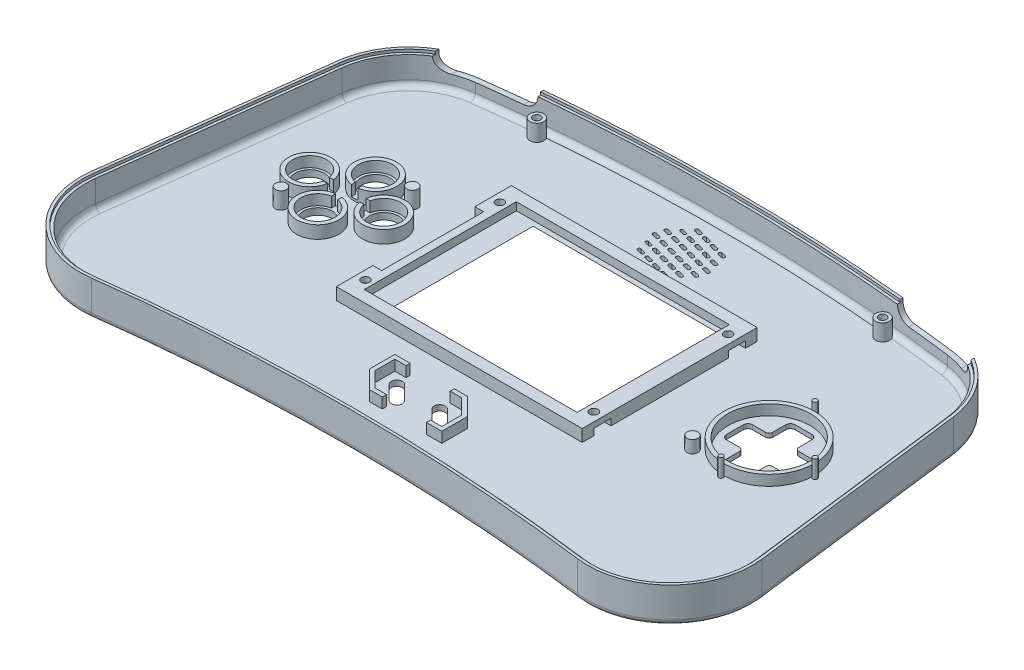
SolidWorks part; units mm, degrees
ref_plane "Plan de face" through (0, 0, 0) normal (0, 0, 1) x (1, 0, 0)
ref_plane "Plan de dessus" through (0, 0, 0) normal (0, 1, 0) x (1, 0, 0)
ref_plane "Plan de droite" through (0, 0, 0) normal (1, 0, 0) x (0, 0, -1)
sketch "Esquisse fond coque" plane through (0, 0, 0) normal (0, 1, 0) x (1, 0, 0)
  line L0 (-122.2671, -38.9175) -> (-112.2671, 40.8662)
  line L1 (112.2671, 40.8662) -> (122.2671, -38.9175)
  line L2 (-103.7302, 58.3314) -> (113.6596, -63.9151) construction
  line L3 (-113.6596, -63.9151) -> (103.7302, 58.3314) construction
  arc A0 (-112.2671, 40.8662) -> (-86.2786, 66.8963) centre (-82.5, 37.1352) cw
  arc A1 (-86.2786, 66.8963) -> (86.2786, 66.8963) centre (0, -612.6484) cw
  arc A2 (86.2786, 66.8963) -> (112.2671, 40.8662) centre (82.5, 37.1352) cw
  arc A3 (-122.2671, -38.9175) -> (-88.6189, -72.3963) centre (-92.5, -42.6484) ccw
  arc A4 (122.2671, -38.9175) -> (88.6189, -72.3963) centre (92.5, -42.6484) cw
  arc A5 (88.6189, -72.3963) -> (-88.6189, -72.3963) centre (0, -751.6398) ccw
  point P14 (122.5, -42.6484)
  point P15 (92.5, -72.6484)
  point P16 (-122.5, -42.6484)
  point P17 (0, 72.3516)
  point P18 (0, -66.6398)
  point P23 (0, 0)
  dimension "D4" = 30
  dimension "D5" = 30
  dimension "D6" = 685
  dimension "D7" = 685
  dimension "D1" = 245
  dimension "D2" = 165
  dimension "D3" = 145
extrude "Fond coque" add sketch "Esquisse fond coque" along normal blind 2
sketch "Esquisse contour coque" plane through (0, 2, 0) normal (0, 1, 0) x (1, 0, 0)
  line L0 (-120.2826, -39.1662) -> (-110.2826, 40.6174)
  line L1 (110.2826, 40.6174) -> (120.2826, -39.1662)
  line L2 (122.2671, -38.9175) -> (112.2671, 40.8662) construction
  line L3 (-112.2671, 40.8662) -> (-122.2671, -38.9175) construction
  line L4 (-122.2671, -38.9175) -> (-112.2671, 40.8662)
  line L5 (112.2671, 40.8662) -> (122.2671, -38.9175)
  arc A0 (-110.2826, 40.6174) -> (-86.0267, 64.9122) centre (-82.5, 37.1352) cw
  arc A1 (-86.0267, 64.9122) -> (86.0267, 64.9122) centre (0, -612.6484) cw
  arc A2 (86.0267, 64.9122) -> (110.2826, 40.6174) centre (82.5, 37.1352) cw
  arc A3 (120.2826, -39.1662) -> (88.8776, -70.4131) centre (92.5, -42.6484) cw
  arc A4 (-120.2826, -39.1662) -> (-88.8776, -70.4131) centre (-92.5, -42.6484) ccw
  arc A5 (-88.8776, -70.4131) -> (88.8776, -70.4131) centre (0, -751.6398) cw
  arc A6 (86.2786, 66.8963) -> (-86.2786, 66.8963) centre (0, -612.6484) ccw construction
  arc A7 (88.6189, -72.3963) -> (-88.6189, -72.3963) centre (0, -751.6398) ccw construction
  arc A8 (-88.6189, -72.3963) -> (-122.2671, -38.9175) centre (-92.5, -42.6484) cw
  arc A9 (-122.2671, -38.9175) -> (-88.6189, -72.3963) centre (-92.5, -42.6484) ccw construction
  arc A10 (88.6189, -72.3963) -> (122.2671, -38.9175) centre (92.5, -42.6484) ccw
  arc A11 (88.6189, -72.3963) -> (122.2671, -38.9175) centre (92.5, -42.6484) ccw construction
  arc A12 (-112.2671, 40.8662) -> (-86.2786, 66.8963) centre (-82.5, 37.1352) cw
  arc A13 (-86.2786, 66.8963) -> (-112.2671, 40.8662) centre (-82.5, 37.1352) ccw construction
  arc A14 (86.2786, 66.8963) -> (112.2671, 40.8662) centre (82.5, 37.1352) cw
  arc A15 (112.2671, 40.8662) -> (86.2786, 66.8963) centre (82.5, 37.1352) ccw construction
  arc A16 (-88.6189, -72.3963) -> (88.6189, -72.3963) centre (0, -751.6398) cw
  arc A17 (-86.2786, 66.8963) -> (86.2786, 66.8963) centre (0, -612.6484) cw
  point P6 (0, 70.3516)
  point P14 (0, -64.6398)
  point P18 (0, 72.3516)
  point P23 (0, -66.6398)
  point P31 (-113.6596, -63.9151)
  point P36 (-113.6596, -63.9151)
  point P37 (0, -66.6398)
  point P39 (113.6596, -63.9151)
  point P45 (113.6596, -63.9151)
  point P54 (-103.7302, 58.3314)
  point P55 (-103.7302, 58.3314)
  point P58 (103.7302, 58.3314)
  point P64 (103.7302, 58.3314)
  point P66 (0, 72.3516)
  dimension "D1" = 2
  dimension "D2" = 2
  dimension "D3" = 2
  dimension "D4" = 2
extrude "Contour coque" add sketch "Esquisse contour coque" along normal blind 10
fillet "Congé1" radius 2 8 edges at (-115.2826, 2, -0.7256) (-102.3148, 2, -56.9183) (0, 2, -70.3516) (102.3148, 2, -56.9183) (115.2826, 2, -0.7256) (112.249, 2, 62.4973) (0, 2, 64.6398) (-112.249, 2, 62.4973)
fillet "Congé2" radius 2 8 edges at (0, 0, 66.6398) (113.6596, 0, 63.9151) (117.2671, 0, -0.9743) (103.7302, 0, -58.3314) (0, 0, -72.3516) (-103.7302, 0, -58.3314) (-117.2671, 0, -0.9743) (-113.6596, 0, 63.9151)
sketch "Esquisse cavité écrou" plane through (0, 0, 0) normal (0, -1, 0) x (1, 0, 0)
  line L1 (33.91, 17.87) -> (-33.91, 17.87)
  line L2 (33.91, 17.87) -> (33.91, -33.87)
  line L3 (33.91, -33.87) -> (-33.91, -33.87)
  line L4 (-33.91, 17.87) -> (-33.91, -33.87)
  line L5 (33.91, 17.87) -> (-33.91, -33.87) construction
  line L6 (33.91, -33.87) -> (-33.91, 17.87) construction
  point P0 (0, -8)
  dimension "D1" = 67.82
  dimension "D2" = 51.74
  dimension "D3" = 8
extrude "Cavité écran" cut sketch "Esquisse cavité écrou" against normal blind 3.55
sketch "Esquisse glissières écran" plane through (0, 2, 0) normal (0, 1, 0) x (1, 0, 0)
  line L1 (-47.84, -23.87) -> (41.72, -23.87)
  line L2 (-47.84, -23.87) -> (-47.84, -19.58)
  line L4 (41.72, -23.87) -> (41.72, -19.58)
  line L29 (-33.91, -17.87) -> (33.91, -17.87) construction
  line L30 (41.72, 35.58) -> (41.72, 39.87)
  line L31 (-33.91, 33.87) -> (-33.91, -17.87) construction
  line L32 (33.91, -17.87) -> (33.91, 33.87) construction
  line L35 (33.91, 33.87) -> (-33.91, 33.87) construction
  line L36 (-47.84, 39.87) -> (41.72, 39.87)
  line L37 (-47.84, 35.58) -> (-44.64, 35.58)
  line L38 (-44.64, 35.58) -> (-41.9553, 34.03)
  line L39 (-47.84, -13.38) -> (-44.64, -13.38)
  line L40 (-44.64, -13.38) -> (-41.9553, -14.93)
  line L41 (35.8353, -14.93) -> (35.8353, -18.03)
  line L42 (35.8353, -18.03) -> (38.52, -19.58)
  line L44 (35.8353, 34.03) -> (35.8353, 30.93)
  line L45 (35.8353, 30.93) -> (38.52, 29.38)
  line L46 (33.91, 33.87) -> (-33.91, 33.87) construction
  line L49 (38.52, 29.38) -> (41.72, 29.38)
  line L50 (35.8353, 34.03) -> (38.52, 35.58)
  line L53 (38.52, -19.58) -> (41.72, -19.58)
  line L60 (-41.9553, -14.93) -> (-41.9553, -18.03)
  line L65 (-41.9553, 34.03) -> (-41.9553, 30.93)
  line L66 (-41.9553, 30.93) -> (-44.64, 29.38)
  line L69 (-41.9553, -18.03) -> (-44.64, -19.58)
  line L70 (-33.91, 33.87) -> (33.91, 33.87)
  line L71 (-33.91, 33.87) -> (-33.91, -17.87)
  line L72 (-33.91, -17.87) -> (33.91, -17.87)
  line L73 (33.91, 33.87) -> (33.91, -17.87)
  line L74 (-44.64, -19.58) -> (-47.84, -19.58)
  line L75 (-47.84, -13.38) -> (-47.84, -10.555)
  line L76 (-44.64, 29.38) -> (-47.84, 29.38)
  line L77 (-47.84, 35.58) -> (-47.84, 39.87)
  line L78 (38.52, 35.58) -> (41.72, 35.58)
  line L79 (38.52, 29.38) -> (38.52, 32.48) construction
  line L80 (38.52, 32.48) -> (38.52, 35.58) construction
  line L81 (35.8353, -14.93) -> (38.52, -13.38)
  line L82 (38.52, -13.38) -> (41.72, -13.38)
  line L83 (38.52, -19.58) -> (38.52, -16.48) construction
  line L84 (38.52, -16.48) -> (38.52, -13.38) construction
  line L85 (41.72, -13.38) -> (41.72, 29.38)
  line L86 (-47.84, 26.555) -> (-44.64, 26.555)
  line L87 (-44.64, 26.555) -> (-44.64, -10.555)
  line L88 (-44.64, -10.555) -> (-47.84, -10.555)
  line L90 (-47.84, 26.555) -> (-47.84, 29.38)
  point P4 (-44.64, 32.48)
  point P12 (38.52, -16.48)
  point P16 (-44.64, -16.48)
  point P18 (38.52, 32.48)
  point P40 (-41.9553, -16.48)
  point P41 (-44.64, 8)
  point P49 (-41.9553, 32.48)
  point P55 (-33.91, 8)
  point P56 (35.8353, 32.48)
  dimension "D2" = 4.61
  dimension "D3" = 6.2
  dimension "D4" = 6.2
  dimension "D5" = 6
  dimension "D6" = 10.73
  dimension "D7" = 3.1
  dimension "D8" = 4.61
  dimension "D9" = 1.39
  dimension "D10" = 10.73
  dimension "D11" = 6.2
  dimension "D12" = 1.39
  dimension "D13" = 6.2
  dimension "D14" = 1.39
  dimension "D15" = 3.2
  dimension "D16" = 3.1
  dimension "D17" = 1.39
  dimension "D18" = 3.2
  dimension "D19" = 3.1
  dimension "D20" = 6
  dimension "D21" = 3.1
  dimension "D22" = 37.11
extrude "Glissières écran" add sketch "Esquisse glissières écran" along normal blind 1.55
chamfer "Chanfrein écran" distance 3.55 angle 45 4 edges at (33.91, 0, -8) (0, 0, 17.87) (-33.91, 0, -8) (0, 0, -33.87)
sketch "Esquisse surélévation écran" plane through (0, 3.55, 0) normal (0, 1, 0) x (1, 0, 0)
  line L0 (-41.84, 35.7) -> (-41.84, -19.7)
  line L1 (-33.91, 33.87) -> (-33.91, -17.87) construction
  line L2 (-47.84, 39.87) -> (-47.84, 35.58)
  line L3 (41.72, 39.87) -> (-47.84, 39.87) construction
  line L4 (-47.84, 35.58) -> (-44.64, 35.58)
  line L5 (-44.64, 35.58) -> (-41.9553, 34.03)
  line L6 (-44.64, 35.58) -> (-41.9553, 34.03) construction
  line L7 (-41.9553, 34.03) -> (-41.9553, 30.93)
  line L8 (-41.9553, 30.93) -> (-44.64, 29.38)
  line L9 (-44.64, 29.38) -> (-47.84, 29.38)
  line L10 (-47.84, 29.38) -> (-47.84, 26.555)
  line L11 (-47.84, -10.555) -> (-47.84, -13.38) construction
  line L14 (-47.84, 26.555) -> (-44.64, 26.555)
  line L15 (-47.84, -13.38) -> (-44.64, -13.38)
  line L16 (-44.64, -13.38) -> (-41.9553, -14.93)
  line L17 (-41.9553, -14.93) -> (-41.9553, -18.03)
  line L18 (-41.9553, -18.03) -> (-44.64, -19.58)
  line L19 (-44.64, -19.58) -> (-47.84, -19.58)
  line L20 (-47.84, -19.58) -> (-47.84, -23.87)
  line L21 (35.72, 35.7) -> (35.72, -19.7)
  line L22 (-44.64, 26.555) -> (-44.64, -10.555)
  line L24 (41.72, 39.87) -> (41.72, 35.58)
  line L25 (41.72, 35.58) -> (38.52, 35.58)
  line L26 (38.52, 35.58) -> (35.8353, 34.03)
  line L27 (35.8353, 34.03) -> (35.8353, 30.93)
  line L28 (35.8353, 30.93) -> (38.52, 29.38)
  line L29 (38.52, 29.38) -> (41.72, 29.38)
  line L30 (41.72, 29.38) -> (41.72, -13.38)
  line L31 (41.72, -13.38) -> (38.52, -13.38)
  line L32 (38.52, -13.38) -> (35.8353, -14.93)
  line L33 (35.8353, -14.93) -> (35.8353, -18.03)
  line L34 (35.8353, -18.03) -> (38.52, -19.58)
  line L35 (38.52, -19.58) -> (41.72, -19.58)
  line L36 (41.72, -19.58) -> (41.72, -23.87)
  line L38 (-47.84, -23.87) -> (41.72, -23.87)
  line L40 (-41.84, -19.7) -> (35.72, -19.7)
  line L42 (-47.84, 39.87) -> (41.72, 39.87)
  line L44 (-41.84, 35.7) -> (35.72, 35.7)
  line L45 (-44.64, -10.555) -> (-47.84, -10.555)
  line L46 (-47.84, -10.555) -> (-47.84, -13.38)
  point P1 (-41.84, 8)
  point P29 (-33.91, 8)
  dimension "D1" = 2.8
  dimension "D2" = 2.8
  dimension "D3" = 55.4
extrude "Surélévation écran" add sketch "Esquisse surélévation écran" along normal blind 0.8
sketch "Esquisse support écran" plane through (0, 4.35, 0) normal (0, 1, 0) x (1, 0, 0)
  line L0 (-47.84, -10.555) -> (-47.84, -23.87)
  line L1 (-47.84, -19.58) -> (-47.84, -23.87) construction
  line L2 (-47.84, -23.87) -> (41.72, -23.87) construction
  line L3 (-47.84, -23.87) -> (41.72, -23.87)
  line L4 (41.72, -23.87) -> (41.72, 39.87)
  line L5 (41.72, 39.87) -> (-47.84, 39.87)
  line L6 (-47.84, 39.87) -> (-47.84, 35.58) construction
  line L7 (41.72, 39.87) -> (-47.84, 39.87) construction
  line L8 (-47.84, 39.87) -> (-47.84, 26.555)
  line L9 (-41.84, -19.7) -> (35.72, -19.7)
  line L10 (35.72, -19.7) -> (35.72, 35.7)
  line L11 (35.72, 35.7) -> (-41.84, 35.7)
  line L12 (-41.84, 35.7) -> (-41.84, -19.7)
  line L13 (35.8353, 30.93) -> (35.8353, 34.03) construction
  line L14 (35.8353, -18.03) -> (35.8353, -14.93) construction
  line L15 (-41.9553, -14.93) -> (-41.9553, -18.03) construction
  line L16 (-41.9553, 34.03) -> (-41.9553, 30.93) construction
  line L17 (-47.84, 26.555) -> (-44.64, 26.555)
  line L19 (-47.84, -10.555) -> (-44.64, -10.555)
  line L20 (-44.64, 26.555) -> (-44.64, -10.555)
  circle A0 centre (-44.64, 32.48) radius 1.5
  circle A1 centre (-44.64, -16.48) radius 1.5
  circle A2 centre (38.52, -16.48) radius 1.5
  circle A3 centre (38.52, 32.48) radius 1.5
  point P35 (35.8353, 32.48)
  point P39 (35.8353, -16.48)
  point P43 (-41.9553, -16.48)
  point P46 (-41.9553, 32.48)
  dimension "D1" = 3
  dimension "D2" = 3
  dimension "D3" = 3
  dimension "D4" = 3
extrude "Support écran" add sketch "Esquisse support écran" along normal blind 2.05
sketch "Esquisse cavités ABXY" plane through (0, 0, 0) normal (0, -1, 0) x (1, 0, 0)
  line L0 (-75.96, -18.5) -> (-75.96, 2.5) construction
  line L1 (-62.46, -8) -> (-89.46, -8) construction
  line L2 (-37.46, -37.42) -> (-37.46, 21.42) construction
  circle A0 centre (-75.96, -18.5) radius 5.3
  circle A1 centre (-75.96, 2.5) radius 5.3
  circle A2 centre (-62.46, -8) radius 5.3
  circle A3 centre (-89.46, -8) radius 5.3
  point P8 (-75.96, -8)
  point P12 (-37.46, -8)
  dimension "D1" = 10.6
  dimension "D2" = 10.6
  dimension "D3" = 10.6
  dimension "D4" = 10.6
  dimension "D5" = 21
  dimension "D6" = 27
  dimension "D8" = 38.5
extrude "Cavités ABXY" cut sketch "Esquisse cavités ABXY" against normal blind 2.05
sketch "Esquisse abaissement ABXY" plane through (0, 0, 0) normal (0, -1, 0) x (-1, 0, 0)
  line L0 (75.9195, 18.4685) -> (62.5005, 8.0315) construction
  line L1 (79.9101, 13.3377) -> (66.4911, 2.9007)
  line L2 (71.9289, 23.5993) -> (58.5099, 13.1623)
  line L3 (75.96, 18.5) -> (62.46, 8) construction
  line L4 (76.0005, -2.4685) -> (89.4195, 7.9685) construction
  line L5 (72.0099, 2.6623) -> (85.4289, 13.0993)
  line L6 (79.9911, -7.5993) -> (93.4101, 2.8377)
  line L7 (75.96, -2.5) -> (89.46, 8) construction
  arc A0 (79.9101, 13.3377) -> (71.9289, 23.5993) centre (75.9195, 18.4685) ccw
  arc A1 (58.5099, 13.1623) -> (66.4911, 2.9007) centre (62.5005, 8.0315) ccw
  arc A2 (72.0099, 2.6623) -> (79.9911, -7.5993) centre (76.0005, -2.4685) ccw
  arc A3 (93.4101, 2.8377) -> (85.4289, 13.0993) centre (89.4195, 7.9685) ccw
  circle A4 centre (62.46, 8) radius 5.3
  circle A5 centre (75.96, 18.5) radius 5.3
  circle A6 centre (75.96, 18.5) radius 5.3 construction
  circle A7 centre (62.46, 8) radius 5.3 construction
  circle A8 centre (75.96, -2.5) radius 5.3
  circle A9 centre (89.46, 8) radius 5.3
  circle A12 centre (75.96, -2.5) radius 5.3 construction
  circle A13 centre (89.46, 8) radius 5.3 construction
  point P2 (69.21, 13.25)
  point P7 (57.3697, 4.0409)
  point P8 (81.0503, 22.4591)
  point P11 (69.21, 13.25)
  point P16 (82.71, 2.75)
  point P25 (82.71, 2.75)
  point P26 (70.8697, -6.4591)
  point P27 (94.5503, 11.9591)
  dimension "D1" = 13
  dimension "D2" = 30
  dimension "D3" = 13
  dimension "D4" = 30
extrude "Enlèv. mat.-Extru.4" cut sketch "Esquisse abaissement ABXY" against normal blind 0.4
sketch "Esquisse support ABXY" plane through (0, 2, 0) normal (0, 1, 0) x (1, 0, 0)
  circle A0 centre (-75.96, 18.5) radius 6.2
  circle A1 centre (-75.96, 18.5) radius 7.7
  circle A2 centre (-89.46, 8) radius 6.2
  circle A3 centre (-89.46, 8) radius 7.7
  circle A4 centre (-75.96, -2.5) radius 6.2
  circle A5 centre (-62.46, 8) radius 6.2
  circle A6 centre (-75.96, -2.5) radius 7.7
  circle A7 centre (-62.46, 8) radius 7.7
  point P4 (-82.16, 18.5)
  point P5 (-83.66, 18.5)
  point P10 (-95.66, 8)
  point P11 (-97.16, 8)
  point P20 (-82.16, -2.5)
  point P21 (-83.66, -2.5)
  point P22 (-68.66, 8)
  point P23 (-70.16, 8)
  dimension "D1" = 12.4
  dimension "D3" = 12.4
  dimension "D5" = 12.4
  dimension "D6" = 12.4
  dimension "D2" = 1.5
  dimension "D4" = 1.5
  dimension "D7" = 1.5
  dimension "D8" = 1.5
extrude "Support ABXY" add sketch "Esquisse support ABXY" along normal blind 4.6
sketch "Esquisse bloquage ABXY" plane through (0, 2, 0) normal (0, 1, 0) x (1, 0, 0)
  line L0 (-75.96, 18.5) -> (-75.96, -2.5) construction
  line L1 (-74.81, 3) -> (-77.11, 3)
  line L2 (-74.81, 3) -> (-74.81, 6.85)
  line L3 (-74.81, 13) -> (-77.11, 13)
  line L4 (-77.11, 3) -> (-77.11, 6.85)
  line L5 (-77.11, 9.15) -> (-74.81, 6.85) construction
  line L6 (-74.81, 9.15) -> (-77.11, 6.85) construction
  line L7 (-62.46, 8) -> (-89.46, 8) construction
  line L8 (-77.11, 9.15) -> (-77.11, 13)
  line L9 (-83.96, 6.85) -> (-77.11, 6.85)
  line L10 (-83.96, 6.85) -> (-83.96, 9.15)
  line L11 (-83.96, 9.15) -> (-77.11, 9.15)
  line L12 (-67.96, 6.85) -> (-67.96, 9.15)
  line L19 (-74.81, 9.15) -> (-74.81, 13)
  line L20 (-74.81, 6.85) -> (-67.96, 6.85)
  line L21 (-74.81, 9.15) -> (-67.96, 9.15)
  point P0 (-75.96, 8)
  point P5 (-75.96, 8)
  point P10 (-75.96, 8)
  point P15 (-75.96, 8)
  dimension "D1" = 2.3
  dimension "D2" = 10
  dimension "D3" = 16
  dimension "D4" = 2.3
extrude "Bloquage ABXY" cut sketch "Esquisse bloquage ABXY" along normal blind 4.6
sketch "Esquisse fixation membrane ABXY" plane through (0, 2, 0) normal (0, 1, 0) x (1, 0, 0)
  line L0 (-89.46, 8) -> (-87.849, -4.0528) construction
  line L1 (-87.849, -4.0528) -> (-75.96, -2.5) construction
  line L2 (-64.071, 20.0528) -> (-75.96, 18.5) construction
  line L3 (-64.071, 20.0528) -> (-62.46, 8) construction
  circle A0 centre (-87.849, -4.0528) radius 2
  circle A1 centre (-64.071, 20.0528) radius 2
  dimension "D3" = 4
  dimension "D4" = 4
  dimension "D1" = 12.16
  dimension "D2" = 11.99
  dimension "D5" = 12.16
  dimension "D6" = 11.99
extrude "Fixation membrane ABXY" add sketch "Esquisse fixation membrane ABXY" along normal blind 6.1
sketch "Esquisse37" plane through (0, 2, 0) normal (0, 1, 0) x (1, 0, 0)
  circle A0 centre (-89.46, 8) radius 5.3
  circle A1 centre (-89.46, 8) radius 5.3 construction
  circle A2 centre (-89.46, 8) radius 7.7
  circle A3 centre (-89.46, 8) radius 6.2 construction
  circle A4 centre (-89.46, 8) radius 7.7 construction
  circle A5 centre (-75.96, 18.5) radius 5.3
  circle A6 centre (-75.96, 18.5) radius 7.7
  circle A7 centre (-62.46, 8) radius 7.7
  circle A8 centre (-62.46, 8) radius 5.3
  circle A9 centre (-75.96, -2.5) radius 5.3
  circle A10 centre (-75.96, -2.5) radius 7.7
  circle A11 centre (-75.96, 18.5) radius 5.3 construction
  circle A12 centre (-75.96, 18.5) radius 7.7 construction
  circle A13 centre (-62.46, 8) radius 5.3 construction
  circle A14 centre (-62.46, 8) radius 7.7 construction
  circle A15 centre (-75.96, -2.5) radius 5.3 construction
  circle A16 centre (-75.96, -2.5) radius 7.7 construction
extrude "Boss.-Extru.4" add sketch "Esquisse37" along normal blind 0.8
sketch "Esquisse cavité DPad" plane through (0, 0, 0) normal (0, -1, 0) x (1, 0, 0)
  line L0 (82.71, -14.0355) -> (82.71, -18.8159)
  line L1 (81.0259, -20.5) -> (74.8941, -20.5)
  line L2 (73.21, -18.8159) -> (73.21, -14.0355)
  line L3 (83.9955, -12.75) -> (88.7759, -12.75)
  line L4 (90.46, -11.0659) -> (90.46, -4.9341)
  line L5 (88.7759, -3.25) -> (83.9955, -3.25)
  line L6 (82.71, -1.9645) -> (82.71, 2.8159)
  line L7 (81.0259, 4.5) -> (74.8941, 4.5)
  line L8 (73.21, 2.8159) -> (73.21, -1.9645)
  line L9 (71.9245, -3.25) -> (67.1441, -3.25)
  line L10 (65.46, -4.9341) -> (65.46, -11.0659)
  line L11 (71.9245, -12.75) -> (67.1441, -12.75)
  line L12 (37.46, 21.42) -> (37.46, -37.42) construction
  line L14 (77.96, -20.5) -> (77.96, 4.5) construction
  line L15 (90.46, -8) -> (65.46, -8) construction
  arc A0 (82.71, -18.8159) -> (81.0259, -20.5) centre (81.0259, -18.8159) cw
  arc A1 (74.8941, -20.5) -> (73.21, -18.8159) centre (74.8941, -18.8159) cw
  arc A2 (82.71, -14.0355) -> (83.9955, -12.75) centre (83.9955, -14.0355) cw
  arc A3 (88.7759, -12.75) -> (90.46, -11.0659) centre (88.7759, -11.0659) ccw
  arc A4 (90.46, -4.9341) -> (88.7759, -3.25) centre (88.7759, -4.9341) ccw
  arc A5 (83.9955, -3.25) -> (82.71, -1.9645) centre (83.9955, -1.9645) cw
  arc A6 (82.71, 2.8159) -> (81.0259, 4.5) centre (81.0259, 2.8159) ccw
  arc A7 (74.8941, 4.5) -> (73.21, 2.8159) centre (74.8941, 2.8159) ccw
  arc A8 (73.21, -1.9645) -> (71.9245, -3.25) centre (71.9245, -1.9645) cw
  arc A9 (67.1441, -3.25) -> (65.46, -4.9341) centre (67.1441, -4.9341) ccw
  arc A10 (73.21, -14.0355) -> (71.9245, -12.75) centre (71.9245, -14.0355) ccw
  arc A11 (67.1441, -12.75) -> (65.46, -11.0659) centre (67.1441, -11.0659) cw
  point P38 (77.96, -8)
  point P41 (82.2167, -20.0067)
  point P42 (65.9533, -3.7433)
  point P43 (83.0865, -13.1265)
  point P44 (72.8335, -2.8735)
  point P46 (37.46, -8)
  point P51 (77.96, -8)
  dimension "D1" = 25
  dimension "D2" = 25
  dimension "D3" = 9.5
  dimension "D4" = 9.5
  dimension "D5" = 23
  dimension "D6" = 14.5
  dimension "D8" = 40.5
extrude "Cavité DPad" cut sketch "Esquisse cavité DPad" against normal blind 2.05
sketch "Cercle alignement" plane through (0, 0, 0) normal (0, -1, 0) x (1, 0, 0)
  circle A0 centre (77.96, -8) radius 7.25
  arc A1 (83.9955, -12.75) -> (82.71, -14.0355) centre (83.9955, -14.0355) ccw construction
  point P6 (83.0865, -13.1265)
sketch "Esquisse support DPad" plane through (0, 2, 0) normal (0, 1, 0) x (1, 0, 0)
  circle A0 centre (77.96, 8) radius 15
  circle A1 centre (77.96, 8) radius 16.5
  point P4 (62.96, 8)
  point P5 (61.46, 8)
  dimension "D1" = 30
  dimension "D2" = 1.5
extrude "Support DPad" add sketch "Esquisse support DPad" along normal blind 3.8
sketch "Esquisse19" plane through (0, 0, 0) normal (0, -1, 0) x (1, 0, 0)
  circle A0 centre (77.96, -8) radius 16
  dimension "D1" = 32
extrude "Abaissement DPad" cut sketch "Esquisse19" against normal blind 0.4
sketch "Esquisse25" plane through (0, 2, 0) normal (0, 1, 0) x (1, 0, 0)
  line L1 (77.96, 8) -> (63.9946, -5.9654) construction
  line L2 (90.46, 8) -> (65.46, 8) construction
  circle A0 centre (63.9946, -5.9654) radius 2
  point P4 (63.9946, -7.9654)
  point P7 (61.9946, -5.9654)
  dimension "D3" = 4
  dimension "D1" = 19.75
  dimension "D2" = 45
extrude "Fixation membrane DPad" add sketch "Esquisse25" along normal blind 4.5
sketch "Esquisse26" plane through (0, 2, 0) normal (0, 1, 0) x (1, 0, 0)
  line L0 (77.7251, -8.4983) -> (94.4583, 8.2349) construction
  line L1 (61.4617, 7.7651) -> (78.1949, 24.4983) construction
  line L2 (94.4583, 8.2349) -> (95.2752, 7.418) construction
  line L4 (67.1441, 3.25) -> (71.9245, 3.25) construction
  line L7 (69.8283, 16.1317) -> (86.0917, -0.1317) construction
  line L8 (63.9946, -5.9654) -> (77.96, 8) construction
  line L10 (78.1949, 24.4983) -> (77.378, 25.3152) construction
  circle A0 centre (77.7134, -9.3232) radius 0.825
  circle A1 centre (95.2752, 7.418) radius 0.825
  circle A2 centre (77.378, 25.3152) radius 0.825
  circle A3 centre (77.96, 8) radius 16.5 construction
  point P9 (78.5384, -9.3232)
  point P26 (63.9946, -5.9654)
  dimension "D1" = 1.65
  dimension "D2" = 1.65
  dimension "D3" = 1.65
  dimension "D5" = 45
  dimension "D8" = 23
  dimension "D9" = 11.5
extrude "Bloquage membrane DPad" add sketch "Esquisse26" along normal blind 6.5 separate body
sketch "Esquisse27" plane through (0, 2, 0) normal (0, 1, 0) x (1, 0, 0)
  line L0 (-10.8, -34.02) -> (-10.8, -35.52)
  line L1 (-10.8, -35.52) -> (-14.9, -35.52)
  line L2 (-14.9, -35.52) -> (-14.9, -42.7046)
  line L3 (-14.9, -42.7046) -> (-9.3846, -48.22)
  line L4 (-9.3846, -48.22) -> (-5.2846, -48.22)
  line L5 (-5.2846, -48.22) -> (-5.2846, -49.72)
  line L6 (-5.2846, -49.72) -> (-10.0059, -49.72)
  line L7 (-10.0059, -49.72) -> (-16.4, -43.3259)
  line L8 (-16.4, -43.3259) -> (-16.4, -34.02)
  line L9 (-16.4, -34.02) -> (-10.8, -34.02)
  line L10 (5.2846, -34.02) -> (5.2846, -35.52)
  line L11 (5.2846, -35.52) -> (9.3846, -35.52)
  line L12 (9.3846, -35.52) -> (14.9, -41.0354)
  line L13 (14.9, -41.0354) -> (14.9, -48.22)
  line L14 (14.9, -48.22) -> (10.8, -48.22)
  line L15 (10.8, -48.22) -> (10.8, -49.72)
  line L16 (10.8, -49.72) -> (16.4, -49.72)
  line L17 (16.4, -49.72) -> (16.4, -40.4141)
  line L18 (16.4, -40.4141) -> (10.0059, -34.02)
  line L19 (10.0059, -34.02) -> (5.2846, -34.02)
  line L20 (-16.4, -34.02) -> (-16.4, -49.72) construction
  line L21 (-16.4, -49.72) -> (16.4, -49.72) construction
  line L22 (16.4, -34.02) -> (-16.4, -34.02) construction
  line L23 (-16.4, -34.02) -> (16.4, -49.72) construction
  line L24 (-16.4, -49.72) -> (16.4, -34.02) construction
  line L25 (16.4, -34.02) -> (16.4, -49.72) construction
  line L28 (-47.84, -23.87) -> (41.72, -23.87) construction
  point P21 (0, -41.87)
  dimension "D1" = 1.5
  dimension "D2" = 1.5
  dimension "D3" = 1.5
  dimension "D4" = 1.5
  dimension "D5" = 1.5
  dimension "D6" = 1.5
  dimension "D7" = 1.5
  dimension "D8" = 1.5
  dimension "D9" = 12.7
  dimension "D10" = 29.8
  dimension "D11" = 7.8
  dimension "D12" = 135
  dimension "D13" = 135
  dimension "D14" = 7.8
  dimension "D15" = 4.1
  dimension "D16" = 4.1
  dimension "D17" = 4.1
  dimension "D18" = 4.1
  dimension "D19" = 18
extrude "Boss.-Extru.1" add sketch "Esquisse27" along normal blind 3.8
sketch "Esquisse28" plane through (0, 2, 0) normal (0, 1, 0) x (1, 0, 0)
  line L0 (-10.3356, -39.3244) -> (-5.2444, -44.4156) construction
  line L1 (-8.9214, -37.9102) -> (-3.8302, -43.0014)
  line L2 (-11.7498, -40.7386) -> (-6.6586, -45.8298)
  line L3 (5.2444, -39.3244) -> (10.3356, -44.4156) construction
  line L4 (6.6586, -37.9102) -> (11.7498, -43.0014)
  line L5 (3.8302, -40.7386) -> (8.9214, -45.8298)
  line L6 (-5.2846, -48.22) -> (-9.3846, -48.22) construction
  line L7 (3.2444, -39.3244) -> (-3.2444, -44.4156) construction
  arc A0 (-8.9214, -37.9102) -> (-11.7498, -40.7386) centre (-10.3356, -39.3244) ccw
  arc A1 (-6.6586, -45.8298) -> (-3.8302, -43.0014) centre (-5.2444, -44.4156) ccw
  arc A2 (6.6586, -37.9102) -> (3.8302, -40.7386) centre (5.2444, -39.3244) ccw
  arc A3 (8.9214, -45.8298) -> (11.7498, -43.0014) centre (10.3356, -44.4156) ccw
  point P2 (-7.79, -41.87)
  point P9 (7.79, -41.87)
  point P16 (-11.7498, -37.9102)
  point P17 (-3.8302, -45.8298)
  point P18 (-10.3356, -37.3244)
  point P19 (5.2444, -37.3244)
  point P20 (10.3356, -46.4156)
  point P21 (-5.2444, -46.4156)
  point P24 (0, -41.87)
  dimension "D1" = 45
  dimension "D2" = 11.2
  dimension "D3" = 4
  dimension "D4" = 15.58
extrude "Enlèv. mat.-Extru.1" cut sketch "Esquisse28" against normal blind 2
sketch "Esquisse29" plane through (0, 2, 0) normal (0, 1, 0) x (1, 0, 0)
  line L0 (-8.9214, -37.9102) -> (-3.8302, -43.0014) construction
  line L1 (6.6586, -37.9102) -> (11.7498, -43.0014) construction
  circle A0 centre (-7.79, -41.87) radius 2
  circle A1 centre (7.79, -41.87) radius 2
sketch3d "Esquisse3D1"
  point P0 (45.3318, 9.2225, -70.8499)
ref_plane "Plan1" through (0, 0, -70.8499) normal (0, 0, -1) x (-1, 0, 0)
sketch "Esquisse30" plane through (0, 0, -70.8499) normal (0, 0, -1) x (-1, 0, 0)
  line L0 (-92.85, 12) -> (-70.15, 12) construction
  line L1 (-92.85, 7.35) -> (-70.15, 7.35)
  line L2 (-97.5, 12) -> (-65.5, 12)
  line L3 (97.5, 12) -> (65.5, 12)
  line L4 (70.15, 7.35) -> (92.85, 7.35)
  line L7 (86.2786, 12) -> (-86.2786, 12) construction
  line L8 (-122.5, 12) -> (-122.5, 2) construction
  line L9 (122.5, 2) -> (122.5, 12) construction
  arc A0 (-97.5, 12) -> (-92.85, 7.35) centre (-92.85, 12) ccw
  arc A1 (-70.15, 7.35) -> (-65.5, 12) centre (-70.15, 12) ccw
  arc A2 (65.5, 12) -> (70.15, 7.35) centre (70.15, 12) ccw
  arc A3 (97.5, 12) -> (92.85, 7.35) centre (92.85, 12) cw
  point P2 (-92.8, 12)
  dimension "D1" = 25
  dimension "D2" = 25
  dimension "D3" = 4.65
  dimension "D4" = 32
  dimension "D5" = 32
  dimension "D6" = 4.65
extrude "Enlèv. mat.-Extru.2" cut sketch "Esquisse30" against normal mid plane 25
sketch "Esquisse31" plane through (0, 2, 0) normal (0, 1, 0) x (1, 0, 0)
  line L1 (65.5, 67.2036) -> (65.5, 69.2128) construction
  line L2 (-65.5, 67.2036) -> (-65.5, 69.2128) construction
  circle A0 centre (-62.98, 64.3036) radius 2.5
  circle A1 centre (-62.98, 64.3036) radius 1.4
  circle A2 centre (62.98, 64.3036) radius 2.5
  circle A3 centre (62.98, 64.3036) radius 1.4
  point P6 (-65.48, 64.3036)
  dimension "D1" = 5
  dimension "D2" = 2.8
  dimension "D3" = 5
  dimension "D4" = 2.8
  dimension "D7" = 2.9
  dimension "D5" = 2.52
  dimension "D6" = 2.9
  dimension "D8" = 2.52
extrude "Boss.-Extru.2" add sketch "Esquisse31" along normal blind 6.04
sketch "Esquisse32" plane through (0, 0, 0) normal (0, -1, 0) x (1, 0, 0)
  line L0 (37.46, -37.42) -> (-37.46, -37.42) construction
  circle A0 centre (0, -53.92) radius 12
  dimension "D1" = 24
  dimension "D2" = 16.5
sketch "Esquisse34" plane through (0, 0, 0) normal (0, -1, 0) x (1, 0, 0)
  line L0 (8.7867, -60.4394) -> (7.2413, -60.8535) construction
  line L3 (8.942, -61.019) -> (7.3966, -61.4331)
  line L6 (8.6315, -59.8598) -> (7.086, -60.2739)
  line L9 (4.923, -61.4747) -> (3.3776, -61.8888) construction
  line L12 (11.9159, -52.5019) -> (-11.0285, -58.6498) construction
  line L13 (10.3305, -60.0257) -> (-5.8936, -64.373) construction
  line L14 (11.0285, -49.1902) -> (-11.9159, -55.3381) construction
  line L15 (9.1416, -46.1462) -> (-11.8037, -51.7585) construction
  line L16 (2.2184, -62.1994) -> (1.3311, -58.8876) construction
  line L17 (1.3311, -58.8876) -> (0.4437, -55.5759) construction
  line L18 (37.46, -37.42) -> (-37.46, -37.42) construction
  line L19 (3.1058, -65.5111) -> (2.2184, -62.1994) construction
  line L20 (11.8037, -56.0815) -> (-9.1416, -61.6938) construction
  line L21 (0.4437, -55.5759) -> (-0.4437, -52.2641) construction
  line L22 (-0.4437, -52.2641) -> (-1.3311, -48.9524) construction
  line L23 (-1.3311, -48.9524) -> (-2.2184, -45.6406) construction
  line L24 (-2.2184, -45.6406) -> (-3.1058, -42.3289) construction
  line L25 (5.8936, -43.467) -> (-10.3305, -47.8143) construction
  line L26 (5.0783, -62.0542) -> (3.5329, -62.4683)
  line L27 (4.7677, -60.8951) -> (3.2223, -61.3092)
  line L28 (1.0593, -62.5099) -> (-0.4861, -62.9241) construction
  line L29 (1.2146, -63.0895) -> (-0.3309, -63.5036)
  line L30 (0.904, -61.9304) -> (-0.6414, -62.3445)
  line L31 (-2.8044, -63.5452) -> (-4.3498, -63.9593) construction
  line L32 (-2.6491, -64.1248) -> (-4.1946, -64.5389)
  line L33 (-2.9597, -62.9657) -> (-4.5051, -63.3798)
  line L34 (10.3305, -60.0257) -> (9.3663, -60.2841) construction
  line L35 (9.8312, -56.61) -> (8.2857, -57.0241) construction
  line L36 (9.9865, -57.1896) -> (8.441, -57.6037)
  line L37 (9.6759, -56.0305) -> (8.1304, -56.4446)
  line L38 (5.9675, -57.6453) -> (4.422, -58.0594) construction
  line L39 (11.8037, -56.0815) -> (-9.1416, -61.6938) construction
  line L40 (6.1228, -58.2248) -> (4.5773, -58.639)
  line L41 (5.8122, -57.0657) -> (4.2667, -57.4798)
  line L42 (2.1038, -58.6806) -> (0.5583, -59.0947) construction
  line L43 (2.2591, -59.2601) -> (0.7136, -59.6742)
  line L44 (1.9485, -58.101) -> (0.403, -58.5151)
  line L45 (-1.7599, -59.7158) -> (-3.3054, -60.1299) construction
  line L46 (-1.6046, -60.2954) -> (-3.1501, -60.7095)
  line L47 (-1.9152, -59.1363) -> (-3.4607, -59.5504)
  line L48 (-5.527, -60.7252) -> (-7.0725, -61.1393) construction
  line L49 (-5.3976, -61.2082) -> (-6.9431, -61.6223)
  line L50 (-5.6564, -60.2423) -> (-7.2019, -60.6564)
  line L51 (10.8757, -52.7806) -> (9.3302, -53.1947) construction
  line L52 (11.031, -53.3602) -> (9.4855, -53.7743)
  line L53 (10.7204, -52.2011) -> (9.1749, -52.6152)
  line L54 (7.012, -53.8159) -> (5.4665, -54.23) construction
  line L55 (7.1673, -54.3955) -> (5.6218, -54.8096)
  line L56 (6.8567, -53.2363) -> (5.3112, -53.6505)
  line L57 (3.1483, -54.8512) -> (1.6028, -55.2653) construction
  line L58 (3.3036, -55.4307) -> (1.7581, -55.8448)
  line L59 (2.993, -54.2716) -> (1.4475, -54.6857)
  line L60 (-0.7154, -55.8865) -> (-2.2609, -56.3006) construction
  line L61 (-0.5601, -56.466) -> (-2.1056, -56.8801)
  line L62 (-0.8707, -55.3069) -> (-2.4162, -55.721)
  line L63 (-4.5791, -56.9217) -> (-6.1246, -57.3358) construction
  line L64 (-4.4238, -57.5013) -> (-5.9693, -57.9154)
  line L65 (-4.7344, -56.3422) -> (-6.2799, -56.7563)
  line L66 (-8.4428, -57.957) -> (-9.9883, -58.3711) construction
  line L67 (-8.2875, -58.5366) -> (-9.833, -58.9507)
  line L68 (-8.5981, -57.3775) -> (-10.1436, -57.7916)
  line L69 (11.0285, -49.1902) -> (-11.9159, -55.3381) construction
  line L70 (9.9883, -49.4689) -> (8.4428, -49.883) construction
  line L71 (10.1436, -50.0484) -> (8.5981, -50.4625)
  line L72 (9.833, -48.8893) -> (8.2875, -49.3034)
  line L73 (6.1246, -50.5042) -> (4.5791, -50.9183) construction
  line L74 (6.2799, -51.0837) -> (4.7344, -51.4978)
  line L75 (5.9693, -49.9246) -> (4.4238, -50.3387)
  line L76 (2.2609, -51.5394) -> (0.7154, -51.9535) construction
  line L77 (2.4162, -52.119) -> (0.8707, -52.5331)
  line L78 (2.1056, -50.9599) -> (0.5601, -51.374)
  line L79 (-1.6028, -52.5747) -> (-3.1483, -52.9888) construction
  line L80 (-1.4475, -53.1543) -> (-2.993, -53.5684)
  line L81 (-1.7581, -51.9952) -> (-3.3036, -52.4093)
  line L82 (-5.4665, -53.61) -> (-7.012, -54.0241) construction
  line L83 (-5.3112, -54.1895) -> (-6.8567, -54.6037)
  line L84 (-5.6218, -53.0304) -> (-7.1673, -53.4445)
  line L85 (-9.3302, -54.6453) -> (-10.8757, -55.0594) construction
  line L86 (-9.1749, -55.2248) -> (-10.7204, -55.6389)
  line L87 (-9.4855, -54.0657) -> (-11.031, -54.4798)
  line L88 (9.1416, -46.1462) -> (-11.8037, -51.7585) construction
  line L89 (7.1691, -46.6748) -> (5.6236, -47.0889) construction
  line L90 (7.3244, -47.2543) -> (5.7789, -47.6684)
  line L91 (7.0138, -46.0952) -> (5.4683, -46.5093)
  line L92 (3.3054, -47.7101) -> (1.7599, -48.1242) construction
  line L93 (3.4607, -48.2896) -> (1.9152, -48.7037)
  line L94 (3.1501, -47.1305) -> (1.6046, -47.5446)
  line L95 (-0.5583, -48.7453) -> (-2.1038, -49.1594) construction
  line L96 (-0.403, -49.3249) -> (-1.9485, -49.739)
  line L97 (-0.7136, -48.1658) -> (-2.2591, -48.5799)
  line L98 (-4.422, -49.7806) -> (-5.9675, -50.1947) construction
  line L99 (-4.2667, -50.3602) -> (-5.8122, -50.7743)
  line L100 (-4.5773, -49.201) -> (-6.1228, -49.6152)
  line L101 (-8.1891, -50.79) -> (-9.7346, -51.2041) construction
  line L102 (-8.0597, -51.273) -> (-9.6052, -51.6871)
  line L103 (-8.3186, -50.307) -> (-9.864, -50.7211)
  line L104 (4.3498, -43.8807) -> (2.8044, -44.2948) construction
  line L105 (4.5051, -44.4602) -> (2.9597, -44.8743)
  line L106 (4.1946, -43.3011) -> (2.6491, -43.7152)
  line L107 (0.4861, -44.9159) -> (-1.0593, -45.3301) construction
  line L108 (5.8936, -43.467) -> (-10.3305, -47.8143) construction
  line L109 (0.6414, -45.4955) -> (-0.904, -45.9096)
  line L110 (0.3309, -44.3364) -> (-1.2146, -44.7505)
  line L111 (-3.3776, -45.9512) -> (-4.923, -46.3653) construction
  line L112 (-3.2223, -46.5308) -> (-4.7677, -46.9449)
  line L113 (-3.5329, -45.3717) -> (-5.0783, -45.7858)
  line L114 (-7.2413, -46.9865) -> (-8.7867, -47.4006) construction
  line L115 (-7.086, -47.5661) -> (-8.6315, -47.9802)
  line L116 (-7.3966, -46.4069) -> (-8.942, -46.821)
  circle A8 centre (0, -53.92) radius 12 construction
  arc A9 (8.942, -61.019) -> (8.6315, -59.8598) centre (8.7867, -60.4394) ccw
  arc A10 (7.086, -60.2739) -> (7.3966, -61.4331) centre (7.2413, -60.8535) ccw
  arc A11 (5.0783, -62.0542) -> (4.7677, -60.8951) centre (4.923, -61.4747) ccw
  arc A12 (3.2223, -61.3092) -> (3.5329, -62.4683) centre (3.3776, -61.8888) ccw
  arc A13 (1.2146, -63.0895) -> (0.904, -61.9304) centre (1.0593, -62.5099) ccw
  arc A14 (-0.6414, -62.3445) -> (-0.3309, -63.5036) centre (-0.4861, -62.9241) ccw
  arc A15 (-2.6491, -64.1248) -> (-2.9597, -62.9657) centre (-2.8044, -63.5452) ccw
  arc A16 (-4.5051, -63.3798) -> (-4.1946, -64.5389) centre (-4.3498, -63.9593) ccw
  arc A17 (9.9865, -57.1896) -> (9.6759, -56.0305) centre (9.8312, -56.61) ccw
  arc A18 (8.1304, -56.4446) -> (8.441, -57.6037) centre (8.2857, -57.0241) ccw
  arc A19 (6.1228, -58.2248) -> (5.8122, -57.0657) centre (5.9675, -57.6453) ccw
  arc A20 (4.2667, -57.4798) -> (4.5773, -58.639) centre (4.422, -58.0594) ccw
  arc A21 (2.2591, -59.2601) -> (1.9485, -58.101) centre (2.1038, -58.6806) ccw
  arc A22 (0.403, -58.5151) -> (0.7136, -59.6742) centre (0.5583, -59.0947) ccw
  arc A23 (-1.6046, -60.2954) -> (-1.9152, -59.1363) centre (-1.7599, -59.7158) ccw
  arc A24 (-3.4607, -59.5504) -> (-3.1501, -60.7095) centre (-3.3054, -60.1299) ccw
  arc A25 (-5.3976, -61.2082) -> (-5.6564, -60.2423) centre (-5.527, -60.7252) ccw
  arc A26 (-7.2019, -60.6564) -> (-6.9431, -61.6223) centre (-7.0725, -61.1393) ccw
  arc A27 (11.031, -53.3602) -> (10.7204, -52.2011) centre (10.8757, -52.7806) ccw
  arc A28 (9.1749, -52.6152) -> (9.4855, -53.7743) centre (9.3302, -53.1947) ccw
  arc A29 (7.1673, -54.3955) -> (6.8567, -53.2363) centre (7.012, -53.8159) ccw
  arc A30 (5.3112, -53.6505) -> (5.6218, -54.8096) centre (5.4665, -54.23) ccw
  arc A31 (3.3036, -55.4307) -> (2.993, -54.2716) centre (3.1483, -54.8512) ccw
  arc A32 (1.4475, -54.6857) -> (1.7581, -55.8448) centre (1.6028, -55.2653) ccw
  arc A33 (-0.5601, -56.466) -> (-0.8707, -55.3069) centre (-0.7154, -55.8865) ccw
  arc A34 (-2.4162, -55.721) -> (-2.1056, -56.8801) centre (-2.2609, -56.3006) ccw
  arc A35 (-4.4238, -57.5013) -> (-4.7344, -56.3422) centre (-4.5791, -56.9217) ccw
  arc A36 (-6.2799, -56.7563) -> (-5.9693, -57.9154) centre (-6.1246, -57.3358) ccw
  arc A37 (-8.2875, -58.5366) -> (-8.5981, -57.3775) centre (-8.4428, -57.957) ccw
  arc A38 (-10.1436, -57.7916) -> (-9.833, -58.9507) centre (-9.9883, -58.3711) ccw
  arc A39 (10.1436, -50.0484) -> (9.833, -48.8893) centre (9.9883, -49.4689) ccw
  arc A40 (8.2875, -49.3034) -> (8.5981, -50.4625) centre (8.4428, -49.883) ccw
  arc A41 (6.2799, -51.0837) -> (5.9693, -49.9246) centre (6.1246, -50.5042) ccw
  arc A42 (4.4238, -50.3387) -> (4.7344, -51.4978) centre (4.5791, -50.9183) ccw
  arc A43 (2.4162, -52.119) -> (2.1056, -50.9599) centre (2.2609, -51.5394) ccw
  arc A44 (0.5601, -51.374) -> (0.8707, -52.5331) centre (0.7154, -51.9535) ccw
  arc A45 (-1.4475, -53.1543) -> (-1.7581, -51.9952) centre (-1.6028, -52.5747) ccw
  arc A46 (-3.3036, -52.4093) -> (-2.993, -53.5684) centre (-3.1483, -52.9888) ccw
  arc A47 (-5.3112, -54.1895) -> (-5.6218, -53.0304) centre (-5.4665, -53.61) ccw
  arc A48 (-7.1673, -53.4445) -> (-6.8567, -54.6037) centre (-7.012, -54.0241) ccw
  arc A49 (-9.1749, -55.2248) -> (-9.4855, -54.0657) centre (-9.3302, -54.6453) ccw
  arc A50 (-11.031, -54.4798) -> (-10.7204, -55.6389) centre (-10.8757, -55.0594) ccw
  arc A51 (7.3244, -47.2543) -> (7.0138, -46.0952) centre (7.1691, -46.6748) ccw
  arc A52 (5.4683, -46.5093) -> (5.7789, -47.6684) centre (5.6236, -47.0889) ccw
  arc A53 (3.4607, -48.2896) -> (3.1501, -47.1305) centre (3.3054, -47.7101) ccw
  arc A54 (1.6046, -47.5446) -> (1.9152, -48.7037) centre (1.7599, -48.1242) ccw
  arc A55 (-0.403, -49.3249) -> (-0.7136, -48.1658) centre (-0.5583, -48.7453) ccw
  arc A56 (-2.2591, -48.5799) -> (-1.9485, -49.739) centre (-2.1038, -49.1594) ccw
  arc A57 (-4.2667, -50.3602) -> (-4.5773, -49.201) centre (-4.422, -49.7806) ccw
  arc A58 (-6.1228, -49.6152) -> (-5.8122, -50.7743) centre (-5.9675, -50.1947) ccw
  arc A59 (-8.0597, -51.273) -> (-8.3186, -50.307) centre (-8.1891, -50.79) ccw
  arc A60 (-9.864, -50.7211) -> (-9.6052, -51.6871) centre (-9.7346, -51.2041) ccw
  arc A61 (4.5051, -44.4602) -> (4.1946, -43.3011) centre (4.3498, -43.8807) ccw
  arc A62 (2.6491, -43.7152) -> (2.9597, -44.8743) centre (2.8044, -44.2948) ccw
  arc A63 (0.6414, -45.4955) -> (0.3309, -44.3364) centre (0.4861, -44.9159) ccw
  arc A64 (-1.2146, -44.7505) -> (-0.904, -45.9096) centre (-1.0593, -45.3301) ccw
  arc A65 (-3.2223, -46.5308) -> (-3.5329, -45.3717) centre (-3.3776, -45.9512) ccw
  arc A66 (-5.0783, -45.7858) -> (-4.7677, -46.9449) centre (-4.923, -46.3653) ccw
  arc A67 (-7.086, -47.5661) -> (-7.3966, -46.4069) centre (-7.2413, -46.9865) ccw
  arc A68 (-8.942, -46.821) -> (-8.6315, -47.9802) centre (-8.7867, -47.4006) ccw
  point P2 (8.014, -60.6464)
  point P9 (4.1503, -61.6817)
  point P14 (0.2866, -62.717)
  point P21 (-3.5771, -63.7523)
  point P36 (-6.2997, -60.9323)
  point P42 (10.1029, -52.9877)
  point P55 (1.6389, -62.3547)
  point P56 (2.798, -62.0441)
  point P57 (5.5026, -61.3194)
  point P58 (6.6617, -61.0088)
  point P59 (-2.2248, -63.3899)
  point P60 (-1.0657, -63.0793)
  point P63 (9.0585, -56.8171)
  point P71 (5.1948, -57.8523)
  point P76 (1.3311, -58.8876)
  point P83 (-2.5326, -59.9229)
  point P104 (7.7062, -57.1794)
  point P105 (6.5471, -57.49)
  point P106 (3.8425, -58.2147)
  point P107 (2.6834, -58.5253)
  point P108 (-0.0212, -59.25)
  point P109 (-1.1803, -59.5605)
  point P110 (-3.8849, -60.2852)
  point P111 (-5.044, -60.5958)
  point P117 (6.2392, -54.023)
  point P124 (2.3755, -55.0582)
  point P131 (-1.4882, -56.0935)
  point P138 (-5.3519, -57.1288)
  point P145 (-9.2156, -58.1641)
  point P153 (1.0232, -55.4206)
  point P154 (-0.1359, -55.7312)
  point P155 (8.7507, -53.35)
  point P156 (7.5915, -53.6606)
  point P157 (3.7278, -54.6959)
  point P158 (4.8869, -54.3853)
  point P159 (-2.8405, -56.4559)
  point P160 (-3.9996, -56.7664)
  point P161 (-6.7042, -57.4911)
  point P162 (-7.8633, -57.8017)
  point P166 (9.2156, -49.6759)
  point P174 (5.3519, -50.7112)
  point P181 (1.4882, -51.7465)
  point P188 (-2.3755, -52.7818)
  point P195 (-6.2392, -53.817)
  point P202 (-10.1029, -54.8523)
  point P209 (0.1359, -52.1088)
  point P210 (-1.0232, -52.4194)
  point P211 (7.8633, -50.0383)
  point P212 (6.7042, -50.3489)
  point P213 (2.8405, -51.3841)
  point P214 (3.9996, -51.0736)
  point P215 (-3.7278, -53.1441)
  point P216 (-4.8869, -53.4547)
  point P217 (-7.5915, -54.1794)
  point P218 (-8.7507, -54.49)
  point P226 (-8.9619, -50.9971)
  point P231 (6.3963, -46.8818)
  point P238 (2.5326, -47.9171)
  point P243 (-1.3311, -48.9524)
  point P250 (-5.1948, -49.9877)
  point P264 (5.044, -47.2442)
  point P265 (3.8849, -47.5548)
  point P266 (1.1803, -48.2795)
  point P267 (0.0212, -48.59)
  point P268 (-2.6834, -49.3147)
  point P269 (-3.8425, -49.6253)
  point P270 (-6.5471, -50.35)
  point P271 (-7.7062, -50.6606)
  point P279 (3.5771, -44.0877)
  point P286 (-0.2866, -45.123)
  point P291 (-4.1503, -46.1583)
  point P298 (-8.014, -47.1936)
  point P308 (-2.798, -45.7959)
  point P309 (-1.6389, -45.4853)
  point P310 (1.0657, -44.7607)
  point P311 (2.2248, -44.4501)
  point P312 (-6.6617, -46.8312)
  point P313 (-5.5026, -46.5206)
  dimension "D1" = 15
  dimension "D2" = 1.6
  dimension "D3" = 1.6
  dimension "D4" = 1.6
  dimension "D5" = 1.6
  dimension "D6" = 1.2
  dimension "D7" = 0.6
  dimension "D8" = 0.6
  dimension "D9" = 1.2
  dimension "D10" = 1.2
  dimension "D11" = 1.2
  dimension "D12" = 1.2
  dimension "D13" = 1.2
  dimension "D14" = 1.2
  dimension "D15" = 1.6
  dimension "D16" = 1.6
  dimension "D17" = 1.6
  dimension "D18" = 1.6
  dimension "D19" = 1.6
  dimension "D20" = 1.2
  dimension "D21" = 1
  dimension "D22" = 1.6
  dimension "D23" = 1.6
  dimension "D24" = 1.6
  dimension "D25" = 1.6
  dimension "D26" = 1.6
  dimension "D27" = 1.6
  dimension "D28" = 0.6
  dimension "D29" = 0.6
  dimension "D30" = 1.2
  dimension "D31" = 1.2
  dimension "D32" = 1.2
  dimension "D33" = 1.2
  dimension "D34" = 1.2
  dimension "D35" = 0.6
  dimension "D36" = 0.6
  dimension "D37" = 1.6
  dimension "D38" = 1.6
  dimension "D39" = 1.6
  dimension "D40" = 1.6
  dimension "D41" = 1.6
  dimension "D42" = 1.2
  dimension "D43" = 1.2
  dimension "D44" = 1.6
  dimension "D45" = 1.2
  dimension "D46" = 1.2
  dimension "D47" = 1.2
  dimension "D48" = 1.2
  dimension "D49" = 1
  dimension "D50" = 1.2
  dimension "D51" = 1.6
  dimension "D52" = 1.2
  dimension "D53" = 1.6
  dimension "D54" = 1.6
  dimension "D55" = 1.6
  dimension "D56" = 1.2
  dimension "D57" = 1.2
  dimension "D58" = 1.6
  dimension "D59" = 0.6
  dimension "D60" = 0.6
  dimension "D61" = 1.2
  dimension "D62" = 1.2
  dimension "D63" = 1.2
  dimension "D64" = 1.6
  dimension "D65" = 1.6
  dimension "D66" = 1.6
  dimension "D67" = 1.6
extrude "Enlèv. mat.-Extru.3" cut sketch "Esquisse34" against normal blind 2
sketch "Esquisse35" plane through (0, 12, 0) normal (0, 1, 0) x (1, 0, 0)
  line L0 (-121.2749, -39.0418) -> (-111.2749, 40.7418)
  line L1 (-110.2826, 40.6174) -> (-120.2826, -39.1662) construction
  line L2 (-108.2981, 40.3687) -> (-110.2826, 40.6174) construction
  line L3 (-120.2826, -39.1662) -> (-118.2981, -39.4149) construction
  line L4 (88.8776, -70.4131) -> (88.6189, -72.3963) construction
  line L5 (121.2749, -39.0418) -> (111.2749, 40.7418)
  line L6 (120.2826, -39.1662) -> (122.2671, -38.9175) construction
  line L9 (122.2671, -38.9175) -> (112.2671, 40.8662) construction
  line L11 (110.2826, 40.6174) -> (112.2671, 40.8662) construction
  line L12 (97.5, 60.7784) -> (97.5, 63.1159) construction
  line L13 (-97.5, 60.7784) -> (-97.5, 63.1159) construction
  line L14 (-65.5, 67.2036) -> (-65.5, 69.2128) construction
  line L15 (65.5, 67.2036) -> (65.5, 69.2128) construction
  line L16 (-122.2671, -38.9175) -> (-112.2671, 40.8662)
  line L17 (-97.5, 63.1159) -> (-97.5, 61.9545)
  line L18 (122.2671, -38.9175) -> (112.2671, 40.8662)
  line L19 (97.5, 63.1159) -> (97.5, 61.9545)
  line L20 (-65.5, 68.2082) -> (-65.5, 69.2128)
  line L21 (65.5, 69.2128) -> (65.5, 68.2082)
  arc A0 (-121.2749, -39.0418) -> (-88.7483, -71.4047) centre (-92.5, -42.6484) ccw
  arc A1 (88.7483, -71.4047) -> (121.2749, -39.0418) centre (92.5, -42.6484) ccw
  arc A2 (88.6189, -72.3963) -> (122.2671, -38.9175) centre (92.5, -42.6484) ccw construction
  arc A3 (-120.2826, -39.1662) -> (-88.8776, -70.4131) centre (-92.5, -42.6484) ccw construction
  arc A4 (-88.7483, -71.4047) -> (88.7483, -71.4047) centre (0, -751.6398) cw
  arc A5 (88.8776, -70.4131) -> (-88.8776, -70.4131) centre (0, -751.6398) ccw construction
  arc A6 (111.2749, 40.7418) -> (97.5, 61.9545) centre (82.5, 37.1352) ccw
  arc A8 (112.2671, 40.8662) -> (97.5, 63.1159) centre (82.5, 37.1352) ccw construction
  arc A9 (-111.2749, 40.7418) -> (-97.5, 61.9545) centre (-82.5, 37.1352) cw
  arc A10 (-97.5, 60.7784) -> (-110.2826, 40.6174) centre (-82.5, 37.1352) ccw construction
  arc A11 (-65.5, 68.2082) -> (65.5, 68.2082) centre (0, -612.6484) cw
  arc A12 (65.5, 69.2128) -> (-65.5, 69.2128) centre (0, -612.6484) ccw construction
  arc A13 (-88.6189, -72.3963) -> (-122.2671, -38.9175) centre (-92.5, -42.6484) cw
  arc A14 (-112.2671, 40.8662) -> (-97.5, 63.1159) centre (-82.5, 37.1352) cw
  arc A15 (-88.6189, -72.3963) -> (88.6189, -72.3963) centre (0, -751.6398) cw
  arc A16 (88.6189, -72.3963) -> (122.2671, -38.9175) centre (92.5, -42.6484) ccw
  arc A17 (97.5, 63.1159) -> (112.2671, 40.8662) centre (82.5, 37.1352) cw
  arc A18 (-65.5, 69.2128) -> (65.5, 69.2128) centre (0, -612.6484) cw
  dimension "D1" = 1
extrude "Boss.-Extru.3" add sketch "Esquisse35" along normal blind 1
